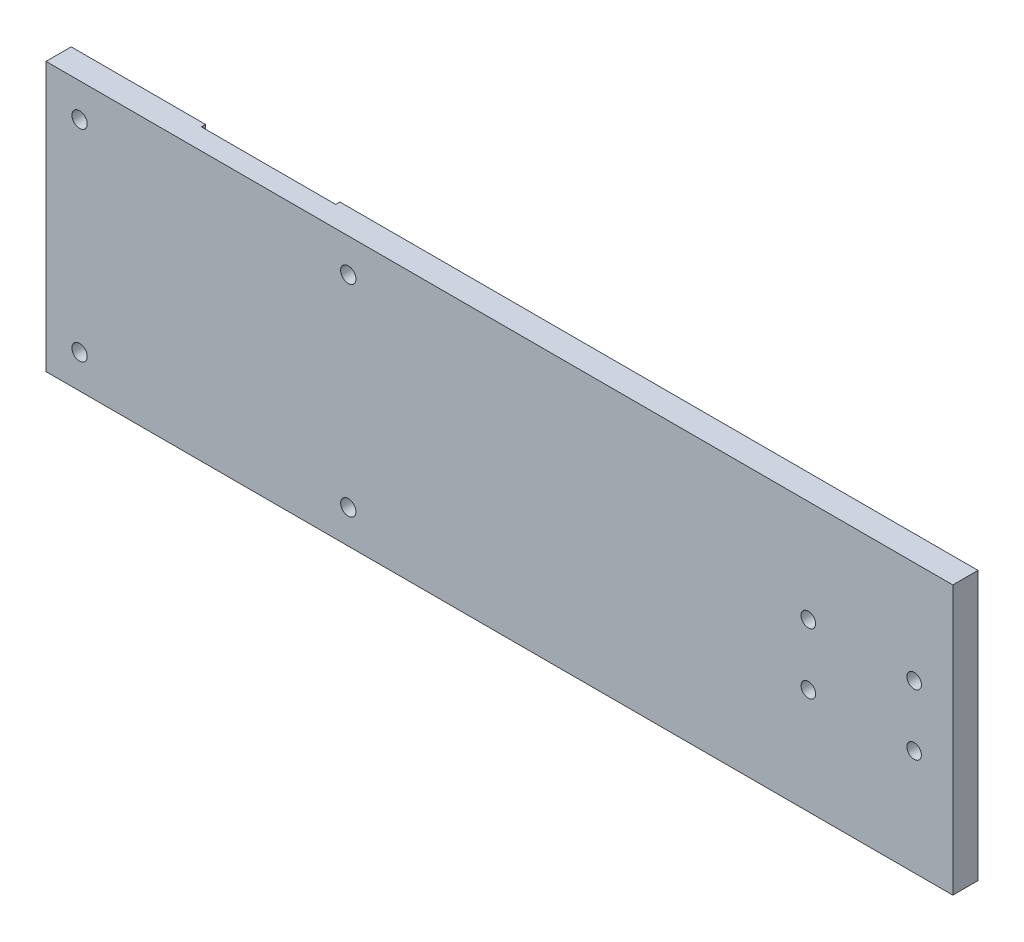
SolidWorks part; units mm, degrees
ref_plane "Front" through (0, 0, 0) normal (0, 0, 1) x (1, 0, 0)
ref_plane "Top" through (0, 0, 0) normal (0, 1, 0) x (1, 0, 0)
ref_plane "Right" through (0, 0, 0) normal (1, 0, 0) x (0, 0, -1)
sketch "Sketch1" plane through (0, 0, 0) normal (0, 0, 1) x (1, 0, 0)
  line L1 (0, 0) -> (342.9, 0)
  line L2 (0, 0) -> (0, 101.6)
  line L3 (0, 101.6) -> (342.9, 101.6)
  line L4 (342.9, 0) -> (342.9, 101.6)
  dimension "D1" = 101.6
  dimension "D2" = 342.9
extrude "Boss-Extrude1" add sketch "Sketch1" along normal blind 9.525
sketch "Sketch2" plane through (0, 0, 0) normal (1, 0, 0) x (0, 0, -1)
  line L0 (0, 0) -> (0, 101.6) construction
  line L1 (0, 76.2) -> (-1.5875, 76.2)
  line L2 (0, 76.2) -> (0, 25.4)
  line L3 (0, 25.4) -> (-1.5875, 25.4)
  line L4 (-1.5875, 76.2) -> (-1.5875, 25.4)
  line L5 (-9.525, 101.6) -> (0, 101.6) construction
  dimension "D1" = 25.4
  dimension "D2" = 50.8
  dimension "D3" = 1.5875
extrude "Cut-Extrude1" cut sketch "Sketch2" against normal blind 9.525 and the other way blind 208.28 from offset 60.325
sketch "Sketch3" plane through (0, 0, 0) normal (0, 0, -1) x (-1, 0, 0)
  line L0 (-342.9, 101.6) -> (0, 101.6) construction
  line L1 (0, 101.6) -> (0, 0) construction
  line L4 (18.8245, 50.8) -> (-106.6282, 50.8) construction
  circle A1 centre (-12.7, 88.9) radius 2.9
  circle A2 centre (-114.3, 88.9) radius 2.9
  circle A3 centre (-114.3, 12.7) radius 2.9
  circle A4 centre (-12.7, 12.7) radius 2.9
  dimension "D1" = 5.8
  dimension "D3" = 12.7
  dimension "D2" = 12.7
  dimension "D4" = 76.2
  dimension "D5" = 101.6
extrude "Cut-Extrude4" cut sketch "Sketch3" against normal through all both
sketch "Sketch5" plane through (0, 0, 0) normal (0, 0, -1) x (-1, 0, 0)
  line L0 (-342.9, 101.6) -> (0, 101.6) construction
  line L1 (-101.6, 101.6) -> (-50.8, 101.6)
  line L2 (-101.6, 101.6) -> (-101.6, 0)
  line L3 (-101.6, 0) -> (-50.8, 0)
  line L4 (-50.8, 101.6) -> (-50.8, 0)
  line L5 (0, 0) -> (-342.9, 0) construction
  line L6 (0, 101.6) -> (0, 0) construction
  dimension "D1" = 50.8
  dimension "D2" = 50.8
extrude "Cut-Extrude5" cut sketch "Sketch5" along direction (0, 0, -1) on the side against the normal up to surface (1.5875 mm away) up to face at (159.7025, 50.8, 1.5875)
hole_wizard "M5 Clearance Hole1" positions "Sketch6" profile "Sketch7" hole size "M5" standard "ANSI Metric" end condition through all
sketch "Sketch6" plane through (0, 0, 9.525) normal (0, 0, 1) x (1, 0, 0)
  line L0 (342.9, 0) -> (342.9, 101.6) construction
  line L1 (0, 0) -> (342.9, 0) construction
  point P0 (328.2696, 62.9412)
  point P2 (328.2696, 39.9288)
  point P4 (288.2646, 39.9288)
  point P6 (288.2646, 62.9412)
  dimension "D1" = 40.005
  dimension "D2" = 14.6304
  dimension "D3" = 39.9288
  dimension "D4" = 23.0124
  dimension "D5" = 14.6304
  dimension "D6" = 40.005
  dimension "D7" = 23.0124
sketch "Sketch7" plane through (328.2696, 62.9412, 9.525) normal (1, 0, 0) x (0, -1, 0)
  line L0 (0, 0) -> (0, 9.525)
  line L1 (0, 9.525) -> (2.75, 9.525)
  line L2 (2.75, 9.525) -> (2.75, 0)
  line L5 (2.75, 0) -> (0, 0)
  line L11 (0, -6.35) -> (0, 107.95) construction
  dimension "Thru Hole Dia." = 5.5
  dimension "Thru Hole Depth" = 9.525
